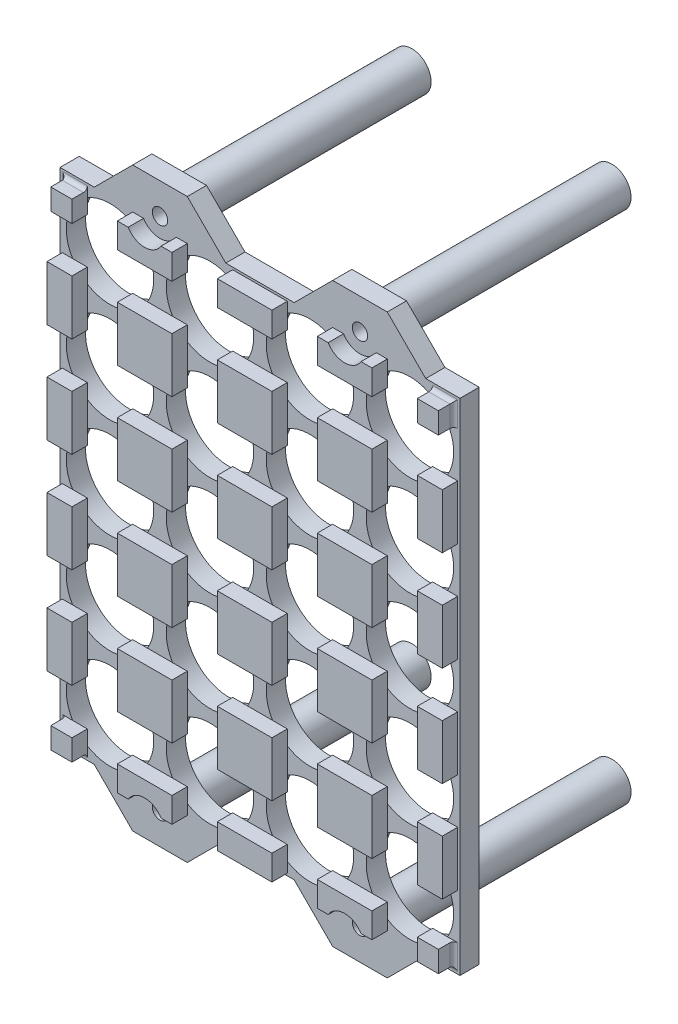
SolidWorks part; units mm, degrees
ref_plane "Front Plane" through (0, 0, 0) normal (0, 0, 1) x (1, 0, 0)
ref_plane "Top Plane" through (0, 0, 0) normal (0, 1, 0) x (1, 0, 0)
ref_plane "Right Plane" through (0, 0, 0) normal (1, 0, 0) x (0, 0, -1)
sketch "Szkic1" plane through (0, 0, 0) normal (0, 0, 1) x (1, 0, 0)
  line L1 (-20.2054, 8.0552) -> (83.7946, 8.0552)
  line L2 (-20.2054, 8.0552) -> (-20.2054, -17.9448)
  line L3 (-20.2054, -17.9448) -> (83.7946, -17.9448)
  line L4 (83.7946, 8.0552) -> (83.7946, -17.9448)
  circle A0 centre (-7.2054, -4.9448) radius 8.854
  circle A1 centre (-7.2054, -4.9448) radius 11.3761
  circle A2 centre (18.7946, -4.9448) radius 8.854
  circle A3 centre (18.7946, -4.9448) radius 11.3761
  circle A4 centre (44.7946, -4.9448) radius 8.854
  circle A5 centre (44.7946, -4.9448) radius 11.3761
  circle A6 centre (70.7946, -4.9448) radius 8.854
  circle A7 centre (70.7946, -4.9448) radius 11.3761
  circle A10 centre (96.7946, -4.9448) radius 8.854 [skipped]
  circle A11 centre (96.7946, -4.9448) radius 11.3761 [skipped]
  dimension "D2" = 13
  dimension "D5" = 13
  dimension "D1" = 5
extrude "Dodanie-wyciągnięcie1" add sketch "Szkic1" along normal blind 5 contours L4 L1 L2 L3 A7 A5 A3 A1 region at (31.7946, -4.9448, 0)
sketch "Szkic15" plane through (0, 0, 0) normal (0, 0, 1) x (1, 0, 0)
  line L6 (-20.2054, -4.9448) -> (-32.3088, -4.9448)
  line L41 (-18.6054, 6.4552) -> (-13.1054, 6.4552)
  line L42 (-18.6054, 6.4552) -> (-18.6054, 0.9552)
  line L43 (-18.6054, 0.9552) -> (-13.1054, 0.9552)
  line L44 (-13.1054, 6.4552) -> (-13.1054, 0.9552)
  line L45 (4.1946, 0.9552) -> (-1.3054, 0.9552)
  line L46 (4.1946, 6.4552) -> (4.1946, 0.9552)
  line L47 (4.1946, 6.4552) -> (-1.3054, 6.4552)
  line L48 (-1.3054, 6.4552) -> (-1.3054, 0.9552)
  line L49 (7.3946, 0.9552) -> (12.8946, 0.9552)
  line L50 (12.8946, 6.4552) -> (12.8946, 0.9552)
  line L51 (7.3946, 6.4552) -> (12.8946, 6.4552)
  line L52 (7.3946, 6.4552) -> (7.3946, 0.9552)
  line L53 (30.1946, 6.4552) -> (24.6946, 6.4552)
  line L54 (24.6946, 6.4552) -> (24.6946, 0.9552)
  line L55 (30.1946, 6.4552) -> (30.1946, 0.9552)
  line L56 (30.1946, 0.9552) -> (24.6946, 0.9552)
  line L57 (33.3946, 0.9552) -> (38.8946, 0.9552)
  line L58 (38.8946, 6.4552) -> (38.8946, 0.9552)
  line L59 (33.3946, 6.4552) -> (38.8946, 6.4552)
  line L60 (33.3946, 6.4552) -> (33.3946, 0.9552)
  line L61 (56.1946, 6.4552) -> (50.6946, 6.4552)
  line L62 (50.6946, 6.4552) -> (50.6946, 0.9552)
  line L63 (56.1946, 6.4552) -> (56.1946, 0.9552)
  line L64 (56.1946, 0.9552) -> (50.6946, 0.9552)
  line L65 (59.3946, 0.9552) -> (64.8946, 0.9552)
  line L66 (64.8946, 6.4552) -> (64.8946, 0.9552)
  line L67 (59.3946, 6.4552) -> (64.8946, 6.4552)
  line L68 (59.3946, 6.4552) -> (59.3946, 0.9552)
  line L69 (82.1946, 6.4552) -> (76.6946, 6.4552)
  line L70 (76.6946, 6.4552) -> (76.6946, 0.9552)
  line L71 (82.1946, 6.4552) -> (82.1946, 0.9552)
  line L72 (82.1946, 0.9552) -> (76.6946, 0.9552)
  line L105 (56.1946, -7.5448) -> (50.6946, -7.5448) [skipped]
  line L106 (56.1946, -7.5448) -> (56.1946, -13.0448) [skipped]
  line L107 (56.1946, -13.0448) -> (50.6946, -13.0448) [skipped]
  line L108 (59.3946, -13.0448) -> (64.8946, -13.0448) [skipped]
  line L109 (64.8946, -7.5448) -> (64.8946, -13.0448) [skipped]
  line L110 (59.3946, -7.5448) -> (64.8946, -7.5448) [skipped]
  line L111 (59.3946, -7.5448) -> (59.3946, -13.0448) [skipped]
  line L112 (82.1946, -7.5448) -> (76.6946, -7.5448) [skipped]
  line L113 (76.6946, -7.5448) -> (76.6946, -13.0448) [skipped]
  line L114 (82.1946, -7.5448) -> (82.1946, -13.0448) [skipped]
  line L115 (82.1946, -13.0448) -> (76.6946, -13.0448) [skipped]
  line L116 (7.3946, -13.0448) -> (12.8946, -13.0448) [skipped]
  line L117 (12.8946, -7.5448) -> (12.8946, -13.0448) [skipped]
  line L118 (7.3946, -7.5448) -> (12.8946, -7.5448) [skipped]
  line L119 (7.3946, -7.5448) -> (7.3946, -13.0448) [skipped]
  line L120 (30.1946, -7.5448) -> (24.6946, -7.5448) [skipped]
  line L121 (24.6946, -7.5448) -> (24.6946, -13.0448) [skipped]
  line L122 (30.1946, -7.5448) -> (30.1946, -13.0448) [skipped]
  line L123 (30.1946, -13.0448) -> (24.6946, -13.0448) [skipped]
  line L124 (33.3946, -13.0448) -> (38.8946, -13.0448) [skipped]
  line L125 (38.8946, -7.5448) -> (38.8946, -13.0448) [skipped]
  line L126 (33.3946, -7.5448) -> (38.8946, -7.5448) [skipped]
  line L127 (33.3946, -7.5448) -> (33.3946, -13.0448) [skipped]
  line L128 (50.6946, -7.5448) -> (50.6946, -13.0448) [skipped]
  line L129 (-18.6054, -13.0448) -> (-13.1054, -13.0448) [skipped]
  line L130 (-13.1054, -7.5448) -> (-13.1054, -13.0448) [skipped]
  line L131 (-18.6054, -7.5448) -> (-13.1054, -7.5448) [skipped]
  line L132 (-18.6054, -7.5448) -> (-18.6054, -13.0448) [skipped]
  line L133 (4.1946, -7.5448) -> (-1.3054, -7.5448) [skipped]
  line L134 (-1.3054, -7.5448) -> (-1.3054, -13.0448) [skipped]
  line L135 (4.1946, -7.5448) -> (4.1946, -13.0448) [skipped]
  line L136 (4.1946, -13.0448) -> (-1.3054, -13.0448) [skipped]
  line L138 (82.1946, -10.8448) -> (76.6946, -10.8448)
  line L139 (82.1946, -16.3448) -> (82.1946, -10.8448)
  line L140 (76.6946, -16.3448) -> (76.6946, -10.8448)
  line L141 (82.1946, -16.3448) -> (76.6946, -16.3448)
  line L142 (59.3946, -16.3448) -> (59.3946, -10.8448)
  line L143 (59.3946, -16.3448) -> (64.8946, -16.3448)
  line L144 (64.8946, -16.3448) -> (64.8946, -10.8448)
  line L145 (59.3946, -10.8448) -> (64.8946, -10.8448)
  line L146 (56.1946, -10.8448) -> (50.6946, -10.8448)
  line L147 (56.1946, -16.3448) -> (56.1946, -10.8448)
  line L148 (50.6946, -16.3448) -> (50.6946, -10.8448)
  line L149 (56.1946, -16.3448) -> (50.6946, -16.3448)
  line L150 (33.3946, -16.3448) -> (33.3946, -10.8448)
  line L151 (33.3946, -16.3448) -> (38.8946, -16.3448)
  line L152 (38.8946, -16.3448) -> (38.8946, -10.8448)
  line L153 (33.3946, -10.8448) -> (38.8946, -10.8448)
  line L154 (30.1946, -10.8448) -> (24.6946, -10.8448)
  line L155 (30.1946, -16.3448) -> (30.1946, -10.8448)
  line L156 (24.6946, -16.3448) -> (24.6946, -10.8448)
  line L157 (30.1946, -16.3448) -> (24.6946, -16.3448)
  line L158 (7.3946, -16.3448) -> (7.3946, -10.8448)
  line L159 (7.3946, -16.3448) -> (12.8946, -16.3448)
  line L160 (12.8946, -16.3448) -> (12.8946, -10.8448)
  line L161 (7.3946, -10.8448) -> (12.8946, -10.8448)
  line L162 (-1.3054, -16.3448) -> (-1.3054, -10.8448)
  line L163 (4.1946, -16.3448) -> (-1.3054, -16.3448)
  line L164 (4.1946, -16.3448) -> (4.1946, -10.8448)
  line L165 (4.1946, -10.8448) -> (-1.3054, -10.8448)
  line L166 (-13.1054, -16.3448) -> (-13.1054, -10.8448)
  line L167 (-18.6054, -10.8448) -> (-13.1054, -10.8448)
  line L168 (-18.6054, -16.3448) -> (-18.6054, -10.8448)
  line L169 (-18.6054, -16.3448) -> (-13.1054, -16.3448)
  point P5 (-18.6054, 6.4552)
  point P71 (-18.6054, -16.3448)
  dimension "D1" = 5.5
extrude "Dodanie-wyciągnięcie7" add sketch "Szkic15" along normal blind 4 from surface contours L167 L166 L169 L168 | L41 L44 L43 L42 | L47 L48 L45 L46 | L51 L50 L49 L52 | L165 L162 L163 L164 | L161 L160 L159 L158 | L53 L54 L56 L55 | L59 L58 L57 L60 | L153 L152 L151 L150 | L154 L156 L157 L155 | L61 L62 L64 L63 | L67 L66 L65 L68 | L145 L144 L143 L142 | L146 L148 L149 L147 | L69 L70 L72 L71 | L138 L140 L141 L139 starting at face at (82.1707, -4.9448, 5)
fillet "Zaokrąglenie9" radius 1 32 edges at (82.1946, 3.7052, 5) (79.4446, 6.4552, 5) (82.1946, -13.5948, 5) (79.4446, -16.3448, 5) (59.3946, 3.7052, 5) (62.1446, 6.4552, 5) (59.3946, -13.5948, 5) (62.1446, -16.3448, 5) (53.4446, -16.3448, 5) (56.1946, -13.5948, 5) (56.1946, 3.7052, 5) (53.4446, 6.4552, 5) (36.1446, 6.4552, 5) (33.3946, 3.7052, 5) (33.3946, -13.5948, 5) (36.1446, -16.3448, 5) (27.4446, -16.3448, 5) (30.1946, -13.5948, 5) (30.1946, 3.7052, 5) (27.4446, 6.4552, 5) (-18.6054, -13.5948, 5) (-15.8554, -16.3448, 5) (10.1446, -16.3448, 5) (1.4446, -16.3448, 5) (4.1946, -13.5948, 5) (7.3946, -13.5948, 5) (7.3946, 3.7052, 5) (10.1446, 6.4552, 5) (4.1946, 3.7052, 5) (1.4446, 6.4552, 5) (-15.8554, 6.4552, 5) (-18.6054, 3.7052, 5)
pattern_linear "Szyk liniowy9" count 5 spacing 26 along (0, 1, 0) of "Dodanie-wyciągnięcie1", "Dodanie-wyciągnięcie7", "Zaokrąglenie9"
sketch "Szkic16" plane through (0, 0, 5) normal (0, 0, 1) x (1, 0, 0)
  line L1 (-1.3054, 93.1552) -> (12.8946, 93.1552)
  line L2 (-1.3054, 93.1552) -> (-1.3054, 78.9552)
  line L3 (-1.3054, 78.9552) -> (12.8946, 78.9552)
  line L4 (12.8946, 93.1552) -> (12.8946, 78.9552)
  line L5 (24.6946, 93.1552) -> (38.8946, 93.1552)
  line L6 (24.6946, 93.1552) -> (24.6946, 78.9552)
  line L7 (24.6946, 78.9552) -> (38.8946, 78.9552)
  line L8 (38.8946, 93.1552) -> (38.8946, 78.9552)
  line L9 (50.6946, 93.1552) -> (64.8946, 93.1552)
  line L10 (50.6946, 93.1552) -> (50.6946, 78.9552)
  line L11 (50.6946, 78.9552) -> (64.8946, 78.9552)
  line L12 (64.8946, 93.1552) -> (64.8946, 78.9552)
  line L13 (-1.3054, 67.1552) -> (12.8946, 67.1552)
  line L14 (-1.3054, 67.1552) -> (-1.3054, 52.9552)
  line L15 (-1.3054, 52.9552) -> (12.8946, 52.9552)
  line L16 (12.8946, 67.1552) -> (12.8946, 52.9552)
  line L17 (24.6946, 67.1552) -> (38.8946, 67.1552)
  line L18 (24.6946, 67.1552) -> (24.6946, 52.9552)
  line L19 (24.6946, 52.9552) -> (38.8946, 52.9552)
  line L20 (38.8946, 67.1552) -> (38.8946, 52.9552)
  line L21 (50.6946, 67.1552) -> (64.8946, 67.1552)
  line L22 (50.6946, 67.1552) -> (50.6946, 52.9552)
  line L23 (50.6946, 52.9552) -> (64.8946, 52.9552)
  line L24 (64.8946, 67.1552) -> (64.8946, 52.9552)
  line L25 (50.6946, 41.1552) -> (64.8946, 41.1552)
  line L26 (50.6946, 41.1552) -> (50.6946, 26.9552)
  line L27 (50.6946, 26.9552) -> (64.8946, 26.9552)
  line L28 (64.8946, 41.1552) -> (64.8946, 26.9552)
  line L29 (24.6946, 41.1552) -> (38.8946, 41.1552)
  line L30 (24.6946, 41.1552) -> (24.6946, 26.9552)
  line L31 (24.6946, 26.9552) -> (38.8946, 26.9552)
  line L32 (38.8946, 41.1552) -> (38.8946, 26.9552)
  line L33 (-1.3054, 41.1552) -> (12.8946, 41.1552)
  line L34 (-1.3054, 41.1552) -> (-1.3054, 26.9552)
  line L35 (-1.3054, 26.9552) -> (12.8946, 26.9552)
  line L36 (12.8946, 41.1552) -> (12.8946, 26.9552)
  line L37 (-1.3054, 15.1552) -> (12.8946, 15.1552)
  line L38 (-1.3054, 15.1552) -> (-1.3054, 0.9552)
  line L39 (-1.3054, 0.9552) -> (12.8946, 0.9552)
  line L40 (12.8946, 15.1552) -> (12.8946, 0.9552)
  line L41 (24.6946, 15.1552) -> (38.8946, 15.1552)
  line L42 (24.6946, 15.1552) -> (24.6946, 0.9552)
  line L43 (24.6946, 0.9552) -> (38.8946, 0.9552)
  line L44 (38.8946, 15.1552) -> (38.8946, 0.9552)
  line L45 (50.6946, 15.1552) -> (64.8946, 15.1552)
  line L46 (50.6946, 15.1552) -> (50.6946, 0.9552)
  line L47 (50.6946, 0.9552) -> (64.8946, 0.9552)
  line L48 (64.8946, 15.1552) -> (64.8946, 0.9552)
  line L49 (-1.3054, 111.4552) -> (12.8946, 111.4552)
  line L50 (-1.3054, 111.4552) -> (-1.3054, 104.9552)
  line L51 (-1.3054, 104.9552) -> (12.8946, 104.9552)
  line L52 (12.8946, 111.4552) -> (12.8946, 104.9552)
  line L53 (24.6946, 111.4552) -> (38.8946, 111.4552)
  line L54 (24.6946, 111.4552) -> (24.6946, 104.9552)
  line L55 (24.6946, 104.9552) -> (38.8946, 104.9552)
  line L56 (38.8946, 111.4552) -> (38.8946, 104.9552)
  line L57 (50.6946, 111.4552) -> (64.8946, 111.4552)
  line L58 (50.6946, 111.4552) -> (50.6946, 104.9552)
  line L59 (50.6946, 104.9552) -> (64.8946, 104.9552)
  line L60 (64.8946, 111.4552) -> (64.8946, 104.9552)
  line L61 (76.6946, 93.1552) -> (83.1946, 93.1552)
  line L62 (76.6946, 93.1552) -> (76.6946, 78.9552)
  line L63 (76.6946, 78.9552) -> (83.1946, 78.9552)
  line L64 (83.1946, 93.1552) -> (83.1946, 78.9552)
  line L65 (76.6946, 67.1552) -> (83.1946, 67.1552)
  line L66 (76.6946, 67.1552) -> (76.6946, 52.9552)
  line L67 (76.6946, 52.9552) -> (83.1946, 52.9552)
  line L68 (83.1946, 67.1552) -> (83.1946, 52.9552)
  line L69 (76.6946, 41.1552) -> (83.1946, 41.1552)
  line L70 (76.6946, 41.1552) -> (76.6946, 26.9552)
  line L71 (76.6946, 26.9552) -> (83.1946, 26.9552)
  line L72 (83.1946, 41.1552) -> (83.1946, 26.9552)
  line L73 (76.6946, 15.1552) -> (83.1946, 15.1552)
  line L74 (76.6946, 15.1552) -> (76.6946, 0.9552)
  line L75 (76.6946, 0.9552) -> (83.1946, 0.9552)
  line L76 (83.1946, 15.1552) -> (83.1946, 0.9552)
  line L77 (50.6946, -10.8448) -> (64.8946, -10.8448)
  line L78 (50.6946, -10.8448) -> (50.6946, -17.3448)
  line L79 (50.6946, -17.3448) -> (64.8946, -17.3448)
  line L80 (64.8946, -10.8448) -> (64.8946, -17.3448)
  line L81 (24.6946, -10.8448) -> (38.8946, -10.8448)
  line L82 (24.6946, -10.8448) -> (24.6946, -17.3448)
  line L83 (24.6946, -17.3448) -> (38.8946, -17.3448)
  line L84 (38.8946, -10.8448) -> (38.8946, -17.3448)
  line L85 (-1.3054, -10.8448) -> (12.8946, -10.8448)
  line L86 (-1.3054, -10.8448) -> (-1.3054, -17.3448)
  line L87 (-1.3054, -17.3448) -> (12.8946, -17.3448)
  line L88 (12.8946, -10.8448) -> (12.8946, -17.3448)
  line L89 (-19.6054, 15.1552) -> (-13.1054, 15.1552)
  line L90 (-19.6054, 15.1552) -> (-19.6054, 0.9552)
  line L91 (-19.6054, 0.9552) -> (-13.1054, 0.9552)
  line L92 (-13.1054, 15.1552) -> (-13.1054, 0.9552)
  line L93 (-19.6054, 41.1552) -> (-13.1054, 41.1552)
  line L94 (-19.6054, 41.1552) -> (-19.6054, 26.9552)
  line L95 (-19.6054, 26.9552) -> (-13.1054, 26.9552)
  line L96 (-13.1054, 41.1552) -> (-13.1054, 26.9552)
  line L97 (-19.6054, 67.1552) -> (-13.1054, 67.1552)
  line L98 (-19.6054, 67.1552) -> (-19.6054, 52.9552)
  line L99 (-19.6054, 52.9552) -> (-13.1054, 52.9552)
  line L100 (-13.1054, 67.1552) -> (-13.1054, 52.9552)
  line L101 (-19.6054, 93.1552) -> (-13.1054, 93.1552)
  line L102 (-19.6054, 93.1552) -> (-19.6054, 78.9552)
  line L103 (-19.6054, 78.9552) -> (-13.1054, 78.9552)
  line L104 (-13.1054, 93.1552) -> (-13.1054, 78.9552)
extrude "Dodanie-wyciągnięcie8" add sketch "Szkic16" along normal blind 4
sketch "Szkic17" plane through (0, 112.0552, 0) normal (0, 1, 0) x (1, 0, 0)
  line L0 (-20.2054, 0) -> (83.7946, 0) construction
  line L1 (-1.3054, -5) -> (12.8946, -5)
  line L2 (-1.3054, -5) -> (-1.3054, 0)
  line L3 (-1.3054, 0) -> (12.8946, 0)
  line L4 (12.8946, -5) -> (12.8946, 0)
  line L5 (50.6946, -9) -> (50.6946, -5) construction
  line L6 (50.6946, 0) -> (64.8946, 0)
  line L7 (50.6946, 0) -> (50.6946, -5)
  line L8 (50.6946, -5) -> (64.8946, -5)
  line L9 (64.8946, 0) -> (64.8946, -5)
  dimension "D1" = 0
extrude "Dodanie-wyciągnięcie9" add sketch "Szkic17" along normal blind 10
ref_plane "Płaszczyzna4" through (0, 47.0552, 0) normal (0, 1, 0) x (1, 0, 0)
sketch "Szkic19" plane through (0, 0, 0) normal (0, 0, -1) x (-1, 0, 0)
  line L0 (-57.7946, 122.0552) -> (-57.7946, 106.6429)
  line L1 (-64.8946, 122.0552) -> (-50.6946, 122.0552) construction
  line L2 (-31.7946, 112.0552) -> (-31.7946, 127.0552)
  line L3 (-12.8946, 112.0552) -> (-50.6946, 112.0552) construction
  circle A0 centre (-57.7946, 114.0552) radius 2
  circle A1 centre (-57.7946, 114.0552) radius 5
  circle A2 centre (-70.7946, 99.0552) radius 11.3761 construction
  circle A3 centre (-5.7946, 114.0552) radius 2
  circle A4 centre (-5.7946, 114.0552) radius 5
  dimension "D1" = 4
  dimension "D2" = 3
  dimension "D3" = 15
extrude "Dodanie-wyciągnięcie10" add sketch "Szkic19" along normal blind 60.5 contours L0 A1 A0 | L0 A1 A0 | A4 A3 region at (55.43, 114.0552, 0) region at (60.1592, 114.0552, 0) region at (10.6532, 114.0552, 0)
extrude "Wytnij-wyciągnięcie2" cut sketch "Szkic19<4>" against normal blind 10 contours A0 | A3
sketch "Szkic19<4>" plane through (0, 0, 0) normal (0, 0, -1) x (-1, 0, 0) same geometry as "Szkic19"
extrude "Wytnij-wyciągnięcie4" cut sketch "Szkic19<6>" against normal blind 10 from surface contours A1 | A4 starting at face at (57.7946, 21.0552, 5)
sketch "Szkic19<6>" plane through (0, 0, 0) normal (0, 0, -1) x (-1, 0, 0) same geometry as "Szkic19"
mirror "Lustro11" about plane through (0, 47.0552, 0) normal (0, 1, 0) of "Wytnij-wyciągnięcie4", "Dodanie-wyciągnięcie9", "Dodanie-wyciągnięcie10", "Wytnij-wyciągnięcie2"
chamfer "Sfazowanie2" distance 10 angle 45 7 edges at (64.8946, -17.9448, 2.5) (50.6946, -17.9448, 2.5) (-1.3054, -17.9448, 2.5) (-1.3054, 112.0552, 2.5) (12.8946, 112.0552, 2.5) (50.6946, 112.0552, 2.5) (64.8946, 112.0552, 2.5)
chamfer "Sfazowanie3" distance 10 angle 45 1 edges at (12.8946, -17.9448, 2.5)
